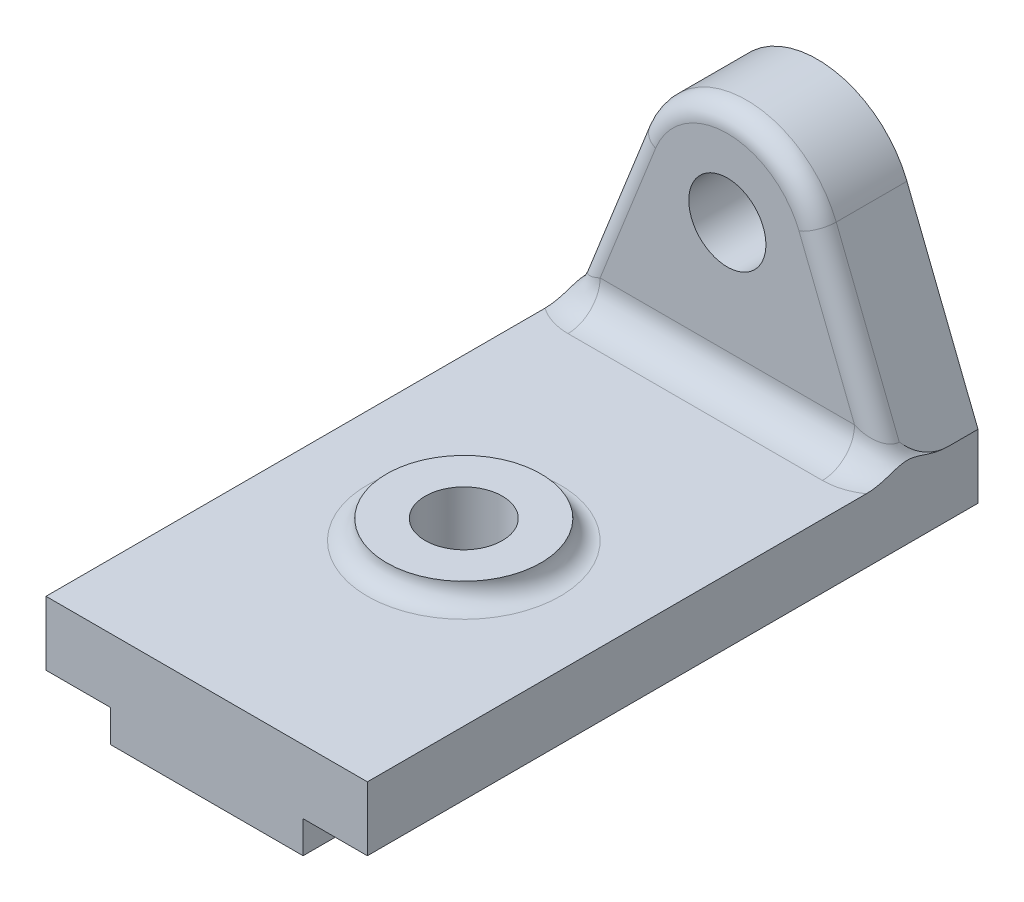
SolidWorks part; units mm, degrees
ref_plane "Ön Düzlem" through (0, 0, 0) normal (0, 0, 1) x (1, 0, 0)
ref_plane "Üst Düzlem" through (0, 0, 0) normal (0, 1, 0) x (1, 0, 0)
ref_plane "Sağ Düzlem" through (0, 0, 0) normal (1, 0, 0) x (0, 0, -1)
sketch "Çizim2" plane through (0, 0, 0) normal (0, 0, 1) x (1, 0, 0)
  line L0 (-25, 0) -> (25, 0)
  line L1 (-15, -14.9666) -> (15, -14.9666)
  line L2 (-25, 0) -> (-25, -9.9666)
  line L3 (-25, -9.9666) -> (-15, -9.9666)
  line L4 (-15, -9.9666) -> (-15, -14.9666)
  line L5 (25, 0) -> (25, -9.9666)
  line L6 (25, -9.9666) -> (15, -9.9666)
  line L7 (15, -9.9666) -> (15, -14.9666)
  point P4 (0, 0)
  point P8 (0, -14.9666)
  dimension "D1" = 50
  dimension "D2" = 30
  dimension "D3" = 18
  dimension "D4" = 5
extrude "Yükseklik-Ekstrüzyon1" add sketch "Çizim2" against normal blind 95
sketch "Çizim3" plane through (0, 0, 0) normal (0, 1, 0) x (1, 0, 0)
  circle A0 centre (0, 40) radius 6
  circle A1 centre (0, 40) radius 12
  dimension "D1" = 12
  dimension "D2" = 24
  dimension "D3" = 40
extrude "Yükseklik-Ekstrüzyon2" add sketch "Çizim3" along normal blind 3
fillet "Radyus1" radius 3 1 edges at (0, 0, -28)
sketch "Çizim4" plane through (0, 0, -95) normal (0, 0, -1) x (-1, 0, 0)
  line L0 (25, 0) -> (13.9445, 27.8909)
  line L1 (-25, 0) -> (-13.9445, 27.8909)
  line L2 (-25, 0) -> (25, 0) construction
  line L3 (-25, 0) -> (25, 0)
  circle A1 centre (0, 22.3635) radius 6
  arc A2 (13.9445, 27.8909) -> (-13.9445, 27.8909) centre (0, 22.3635) ccw
  dimension "D1" = 12
  dimension "D2" = 30
extrude "Yükseklik-Ekstrüzyon3" add sketch "Çizim4" against normal blind 14
sketch "Çizim6" plane through (0, 0, 0) normal (0, 1, 0) x (1, 0, 0)
  circle A0 centre (0, 40) radius 6
extrude "Kes-Ekstrüzyon1" cut sketch "Çizim6" against normal blind 55
fillet "Radyus4" radius 3 3 edges at (-19.4722, 13.9454, -81) (0, 37.3635, -81) (19.4722, 13.9454, -81)
fillet "Radyus5" radius 5 3 edges at (24.0548, 0, -81.8787) (-24.0548, 0, -81.8787) (0, 0, -81)
